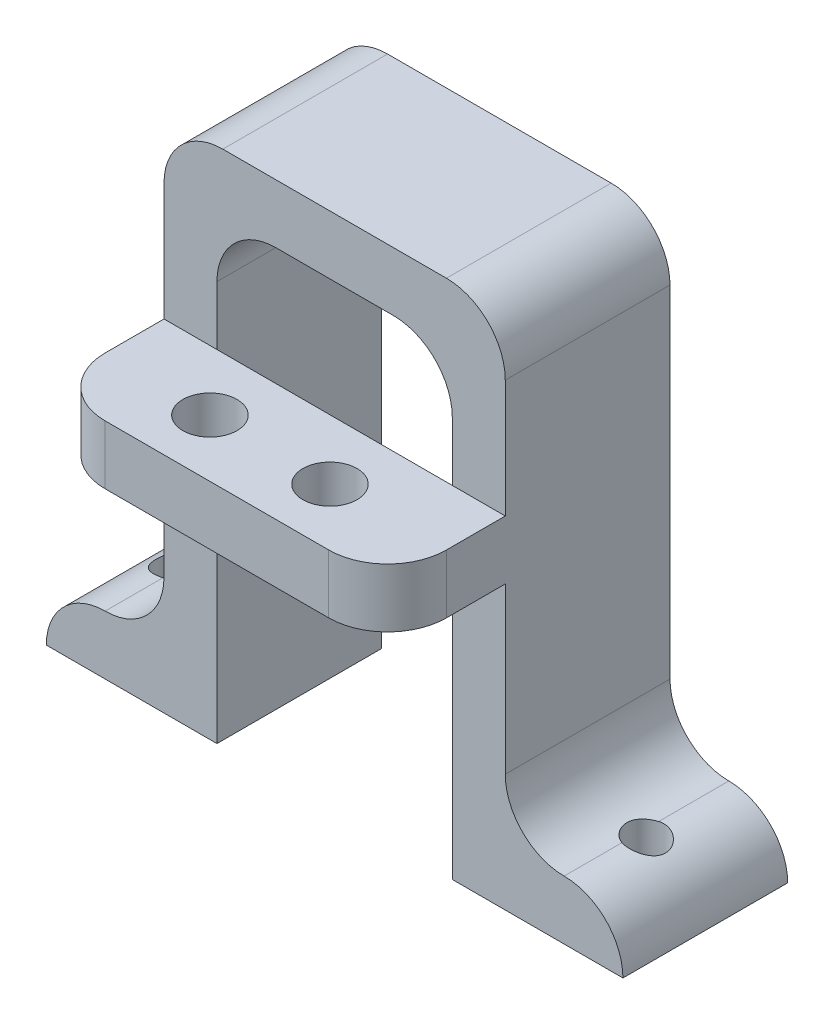
SolidWorks part; units mm, degrees
ref_plane "Front Plane" through (0, 0, 0) normal (0, 0, 1) x (1, 0, 0)
ref_plane "Top Plane" through (0, 0, 0) normal (0, 1, 0) x (1, 0, 0)
ref_plane "Right Plane" through (0, 0, 0) normal (1, 0, 0) x (0, 0, -1)
sketch "Sketch1" plane through (0, 0, 0) normal (0, 0, 1) x (1, 0, 0)
  line L0 (-24.5, 0) -> (-24.5, 5)
  line L1 (7.7, 0) -> (-7.7, 0) construction
  line L2 (-24.5, 5) -> (-14.5, 5)
  line L3 (-14.5, 5) -> (-14.5, 44)
  line L4 (-14.5, 44) -> (14.5, 44)
  line L5 (-24.5, 0) -> (-10, 0)
  line L6 (-10, 0) -> (-10, 39)
  line L7 (-10, 39) -> (10, 39)
  line L8 (0, -16.5) -> (0, 16.5) construction
  line L9 (24.5, 0) -> (10, 0)
  line L10 (24.5, 0) -> (24.5, 5)
  line L11 (24.5, 5) -> (14.5, 5)
  line L12 (10, 0) -> (10, 39)
  line L13 (14.5, 5) -> (14.5, 44)
  point P7 (0, 39)
  point P19 (0, 44)
  dimension "D1" = 20
  dimension "D2" = 5
  dimension "D4" = 5
  dimension "D6" = 39
extrude "Boss-Extrude1" add sketch "Sketch1" along normal blind 14
fillet "Fillet1" radius 5 6 edges at (-14.5, 44, 7) (14.5, 44, 7) (24.5, 5, 7) (-24.5, 5, 7) (14.5, 5, 7) (-14.5, 5, 7)
fillet "Fillet2" radius 5 2 edges at (10, 39, 7) (-10, 39, 7)
sketch "Sketch2" plane through (0, 0, 0) normal (0, 1, 0) x (1, 0, 0)
  line L0 (0, -16.5) -> (0, 16.5) construction
  circle A0 centre (-20, -7.5233) radius 1.636
  circle A1 centre (20, -7.5233) radius 1.636
  dimension "D1" = 40
extrude "Cut-Extrude3" cut sketch "Sketch2" against normal blind 10 and the other way blind 10 contours A0 | A1
sketch "Sketch4" plane through (0, 0, 14) normal (0, 0, 1) x (1, 0, 0)
  line L0 (-14.5, 39) -> (-14.5, 10) construction
  line L1 (9.5, 44) -> (-9.5, 44)
  line L2 (9.5, 44) -> (9.5, 39)
  line L3 (9.5, 39) -> (-9.5, 39)
  line L4 (-9.5, 44) -> (-9.5, 39)
  line L5 (-14.5, 29) -> (14.5, 29)
  line L6 (-14.5, 29) -> (-14.5, 24)
  line L7 (-14.5, 24) -> (14.5, 24)
  line L8 (14.5, 29) -> (14.5, 24)
  line L9 (14.5, 10) -> (14.5, 39) construction
  dimension "D1" = 15
  dimension "D2" = 5
extrude "Boss-Extrude2" add sketch "Sketch4" along normal blind 10 contours L6 L5 L8 L7
sketch "Sketch5" plane through (0, 44, 0) normal (0, 1, 0) x (1, 0, 0)
  circle A2 centre (-5.4774, -19.1181) radius 2.3
  circle A3 centre (4.7058, -19.1015) radius 2.3
  point P8 (0, 0)
  point P9 (4.7058, -15.7949)
  dimension "D3" = 4.6
  dimension "D4" = 4.6
extrude "Cut-Extrude4" cut sketch "Sketch5" against normal blind 30 contours A2 | A3 region at (-5.4774, 44, 19.1181) region at (4.7058, 44, 19.1015)
fillet "Fillet3" radius 5 2 edges at (-14.5, 26.5, 24) (14.5, 26.5, 24)
